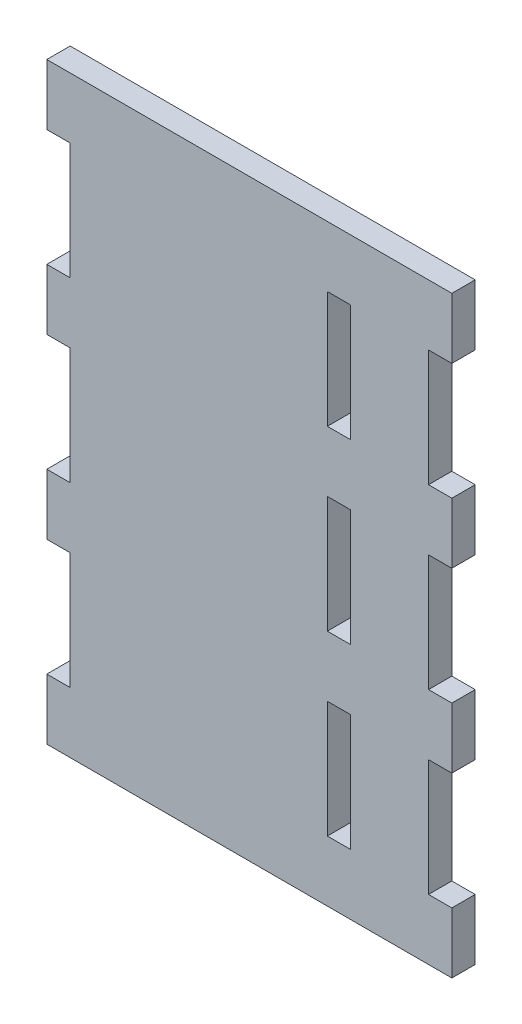
SolidWorks part; units mm, degrees
material "Oak"
ref_plane "Front Plane" through (0, 0, 0) normal (0, 0, 1) x (1, 0, 0)
ref_plane "Top Plane" through (0, 0, 0) normal (0, 1, 0) x (1, 0, 0)
ref_plane "Right Plane" through (0, 0, 0) normal (1, 0, 0) x (0, 0, -1)
sketch "Sketch1" plane through (0, 0, 0) normal (0, 0, 1) x (1, 0, 0)
  line L1 (-40.9935, 16.542) -> (11.0565, 16.542)
  line L2 (-40.9935, 16.542) -> (-40.9935, -59.658)
  line L3 (-40.9935, -59.658) -> (11.0565, -59.658)
  line L4 (11.0565, 16.542) -> (11.0565, -59.658)
  dimension "D1" = 76.2
  dimension "D2" = 52.05
extrude "Boss-Extrude1" add sketch "Sketch1" along normal blind 3
sketch "Sketch2" plane through (0, 0, 3) normal (0, 0, 1) x (1, 0, 0)
  line L0 (-40.9935, 16.542) -> (-40.9935, -59.658) construction
  line L1 (-40.9935, 8.742) -> (-37.9935, 8.742)
  line L2 (-40.9935, 8.742) -> (-40.9935, -6.258)
  line L3 (-40.9935, -6.258) -> (-37.9935, -6.258)
  line L4 (-37.9935, 8.742) -> (-37.9935, -6.258)
  line L5 (11.0565, 16.542) -> (-40.9935, 16.542) construction
  line L6 (11.0565, -59.658) -> (11.0565, 16.542) construction
  line L7 (11.0565, 8.742) -> (8.0565, 8.742)
  line L8 (11.0565, 8.742) -> (11.0565, -6.258)
  line L9 (11.0565, -6.258) -> (8.0565, -6.258)
  line L10 (8.0565, 8.742) -> (8.0565, -6.258)
  point P8 (-39.4935, 8.742)
  dimension "D1" = 3
  dimension "D2" = 7.8
  dimension "D3" = 15
  dimension "D4" = 3
  dimension "D5" = 7.8
  dimension "D6" = 15
extrude "Cut-Extrude1" cut sketch "Sketch2" against normal through all
pattern_linear "LPattern1" count 3 spacing 22.8 along (0, -1, 0) of "Cut-Extrude1"
sketch "Sketch3" plane through (0, 0, 3) normal (0, 0, 1) x (1, 0, 0)
  line L0 (-40.9935, 16.542) -> (-40.9935, 8.742) construction
  line L1 (-4.9435, 8.742) -> (-1.9435, 8.742)
  line L2 (-4.9435, 8.742) -> (-4.9435, -6.258)
  line L3 (-4.9435, -6.258) -> (-1.9435, -6.258)
  line L4 (-1.9435, 8.742) -> (-1.9435, -6.258)
  line L5 (11.0565, 16.542) -> (-40.9935, 16.542) construction
  dimension "D1" = 36.05
  dimension "D2" = 7.8
  dimension "D3" = 3
  dimension "D4" = 15
extrude "Cut-Extrude2" cut sketch "Sketch3" against normal through all
pattern_linear "LPattern2" count 3 spacing 22.8 along (0, -1, 0) of "Cut-Extrude2"
